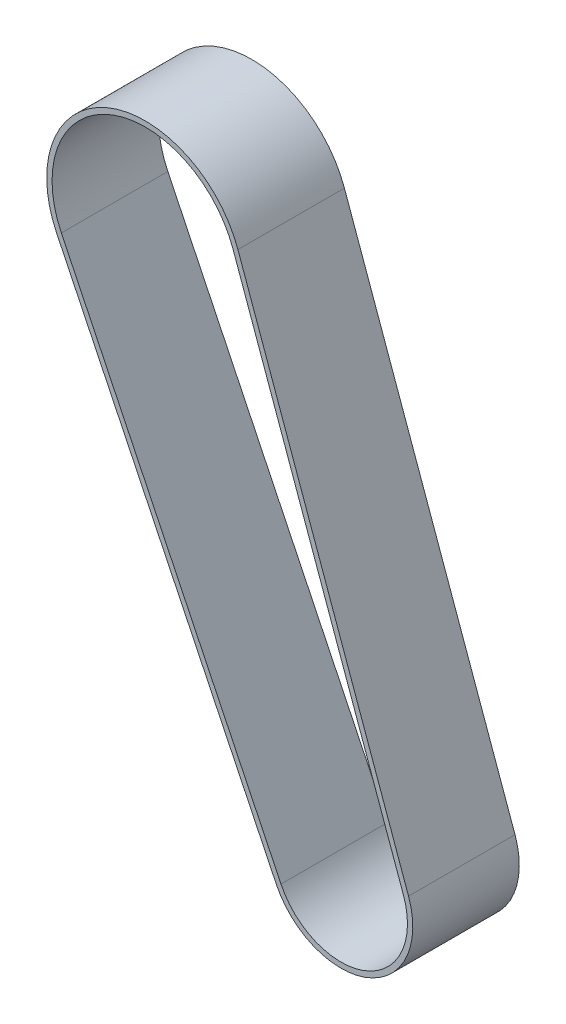
SolidWorks part; units mm, degrees
ref_plane "Спереди" through (0, 0, 0) normal (0, 0, 1) x (1, 0, 0)
ref_plane "Сверху" through (0, 0, 0) normal (0, 1, 0) x (1, 0, 0)
ref_plane "Справа" through (0, 0, 0) normal (1, 0, 0) x (0, 0, -1)
ref_axis "ОсьX" through (-88.99, 0, 0) along (1, 0, 0)
ref_axis "ОсьZ" through (0, 55, 0) along (0, -1, 0)
ref_axis "ОсьY" through (0, 0, -88.99) along (0, 0, 1)
sketch "Эскиз1" plane through (0, 0, 0) normal (0, 0, 1) x (1, 0, 0)
  line L0 (-15.7538, -7.6202) -> (25.4981, -92.9037)
  line L1 (16.4684, 5.9195) -> (48.514, -83.2325)
  arc A0 (-5.9616, 16.4533) -> (-7.4188, 15.8497) centre (0, 0) ccw construction
  arc A1 (16.4684, 5.9195) -> (-15.7538, -7.6202) centre (0, 0) ccw
  arc A2 (26.6342, -94.8027) -> (27.8636, -96.2509) centre (36.7508, -87.4607) ccw construction
  arc A3 (25.4981, -92.9037) -> (48.514, -83.2325) centre (36.7508, -87.4607) ccw
extrude "Вытянуть-Тонкостенный1" add sketch "Эскиз1" along normal blind 20 thin thin type one direction wall 1
